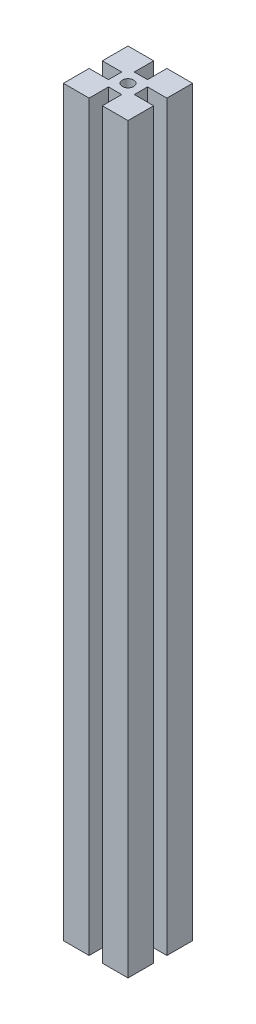
SolidWorks part; units mm, degrees
ref_plane "Ebene vorne" through (0, 0, 0) normal (0, 0, 1) x (1, 0, 0)
ref_plane "Ebene oben" through (0, 0, 0) normal (0, 1, 0) x (1, 0, 0)
ref_plane "Ebene rechts" through (0, 0, 0) normal (1, 0, 0) x (0, 0, -1)
sketch "Skizze1" plane through (0, 0, 0) normal (0, 1, 0) x (1, 0, 0)
  line L0 (-4.1, -20) -> (-4.1, -8)
  line L1 (-20, 20) -> (-4.1, 20)
  line L2 (-20, 20) -> (-20, 4.1)
  line L3 (-20, -20) -> (-4.1, -20)
  line L4 (20, 20) -> (20, 4.1)
  line L5 (-20, 20) -> (20, -20) construction
  line L6 (-20, -20) -> (20, 20) construction
  line L7 (-4.1, -8) -> (4.1, -8)
  line L8 (4.1, -8) -> (4.1, -20)
  line L9 (0, 53.9798) -> (0, -29.8049) construction
  line L10 (4.1, -20) -> (20, -20)
  line L11 (-42.3353, 0) -> (35.9872, 0) construction
  line L12 (4.1, 8) -> (4.1, 20)
  line L13 (-4.1, 20) -> (-4.1, 8)
  line L14 (-4.1, 8) -> (4.1, 8)
  line L15 (4.1, 20) -> (20, 20)
  line L16 (-20, 4.1) -> (-8, 4.1)
  line L17 (-8, 4.1) -> (-8, -4.1)
  line L18 (-8, -4.1) -> (-20, -4.1)
  line L19 (-20, -4.1) -> (-20, -20)
  line L20 (8, 4.1) -> (8, -4.1)
  line L21 (8, -4.1) -> (20, -4.1)
  line L22 (20, 4.1) -> (8, 4.1)
  line L23 (20, -4.1) -> (20, -20)
  circle A0 centre (0, 0) radius 3.5
  point P0 (0, 0)
  dimension "D7" = 7
  dimension "D1" = 40
  dimension "D2" = 8.2
  dimension "D3" = 12
  dimension "D4" = 40
  dimension "D5" = 8.2
  dimension "D6" = 12
extrude "Aufsatz-Linear austragen1" add sketch "Skizze1" along normal blind 230 and the other way blind 230
